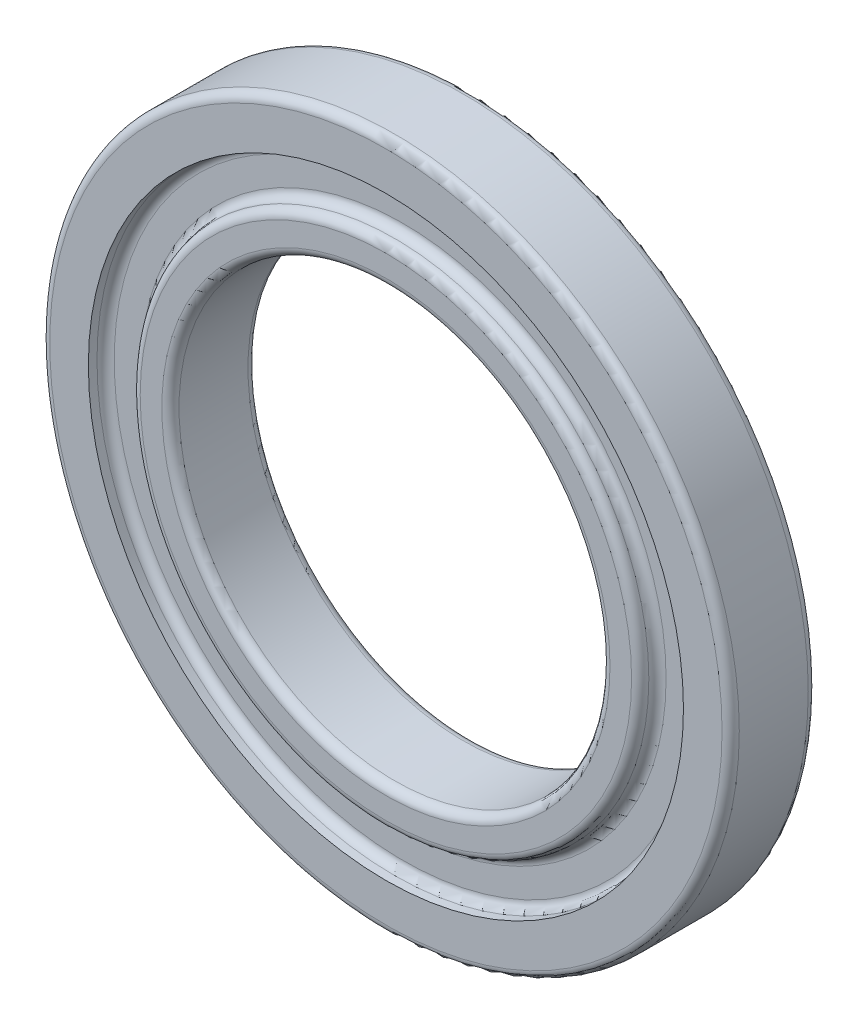
SolidWorks part; units mm, degrees
ref_plane "Front Plane" through (0, 0, 0) normal (0, 0, 1) x (1, 0, 0)
ref_plane "Top Plane" through (0, 0, 0) normal (0, 1, 0) x (1, 0, 0)
ref_plane "Right Plane" through (0, 0, 0) normal (1, 0, 0) x (0, 0, -1)
sketch "Sketch1" plane through (0, 0, 0) normal (0, 0, 1) x (1, 0, 0)
  circle A0 centre (0, 0) radius 0.25
  circle A1 centre (0, 0) radius 0.4
  dimension "D1" = 0.5
  dimension "D2" = 0.8
extrude "Boss-Extrude1" add sketch "Sketch1" along normal mid plane 0.1
sketch "Sketch2" plane through (0, 0, 0.05) normal (0, 0, 1) x (1, 0, 0)
  circle A0 centre (0, 0) radius 0.3452
  circle A1 centre (0, 0) radius 0.2951
extrude "Cut-Extrude1" cut sketch "Sketch2" against normal blind 0.02
mirror "Mirror1" about plane through (0, 0, 0) normal (0, 0, 1) of "Cut-Extrude1"
fillet "Fillet1" radius 0.01 8 edges at (0.2951, 0, -0.03) (0.2951, 0, 0.03) (0.3452, 0, 0.03) (0.3452, 0, -0.03) (0.2951, 0, -0.05) (0.4, 0, -0.05) (0.4, 0, 0.05) (0.2951, 0, 0.05)
fillet "Fillet2" radius 0.01 2 edges at (0.25, 0, -0.05) (0.25, 0, 0.05)
